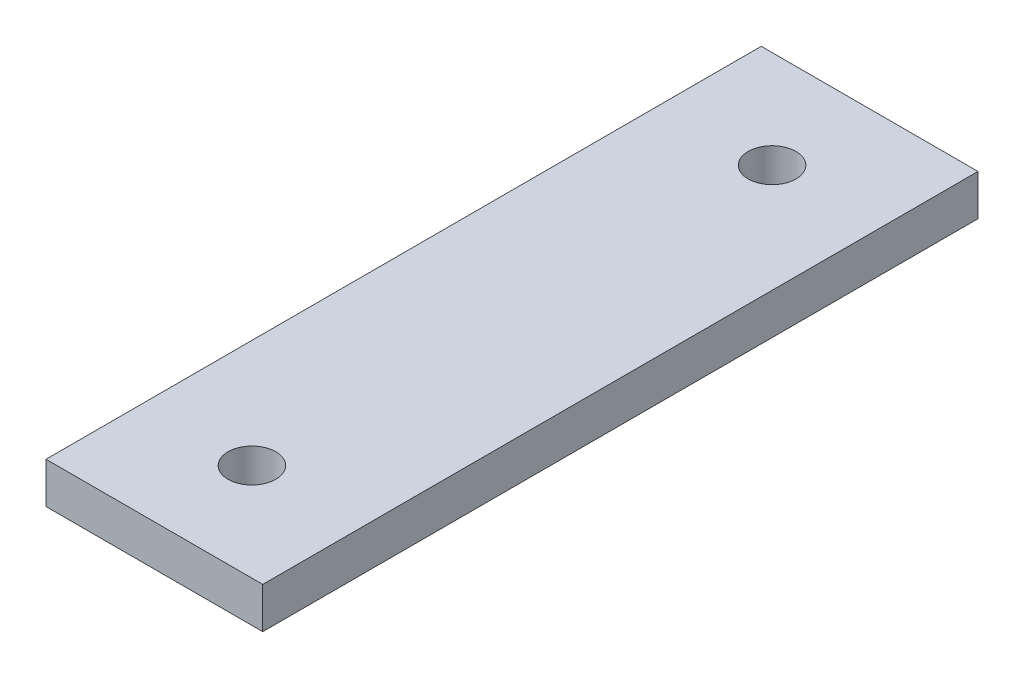
SolidWorks part; units mm, degrees
ref_plane "Front Plane" through (0, 0, 0) normal (0, 0, 1) x (1, 0, 0)
ref_plane "Top Plane" through (0, 0, 0) normal (0, 1, 0) x (1, 0, 0)
ref_plane "Right Plane" through (0, 0, 0) normal (1, 0, 0) x (0, 0, -1)
sketch "Sketch1" plane through (0, 0, 0) normal (0, 1, 0) x (1, 0, 0)
  line L1 (-12.7, -79.775) -> (19.05, -79.775)
  line L2 (-12.7, -79.775) -> (-12.7, 25)
  line L3 (-12.7, 25) -> (19.05, 25)
  line L4 (19.05, -79.775) -> (19.05, 25)
  point P4 (3.175, -79.775)
  point P5 (0, 0)
  dimension "D1" = 104.775
  dimension "D2" = 31.75
extrude "Boss-Extrude1" add sketch "Sketch1" along normal blind 6
sketch "Sketch2" plane through (0, 6, 0) normal (0, 1, 0) x (1, 0, 0)
  line L0 (3.175, 25) -> (3.175, -79.775) construction
  line L1 (19.05, 25) -> (-12.7, 25) construction
  line L2 (-12.7, -79.775) -> (19.05, -79.775) construction
  line L3 (19.05, -27.3875) -> (-12.7, -27.3875) construction
  line L4 (19.05, -79.775) -> (19.05, 25) construction
  line L5 (-12.7, 25) -> (-12.7, -79.775) construction
  circle A0 centre (3.175, 10.7125) radius 3.5
  circle A1 centre (3.175, -65.4875) radius 3.5
  dimension "D1" = 7
  dimension "D2" = 14.2875
extrude "Cut-Extrude1" cut sketch "Sketch2" against normal through all
